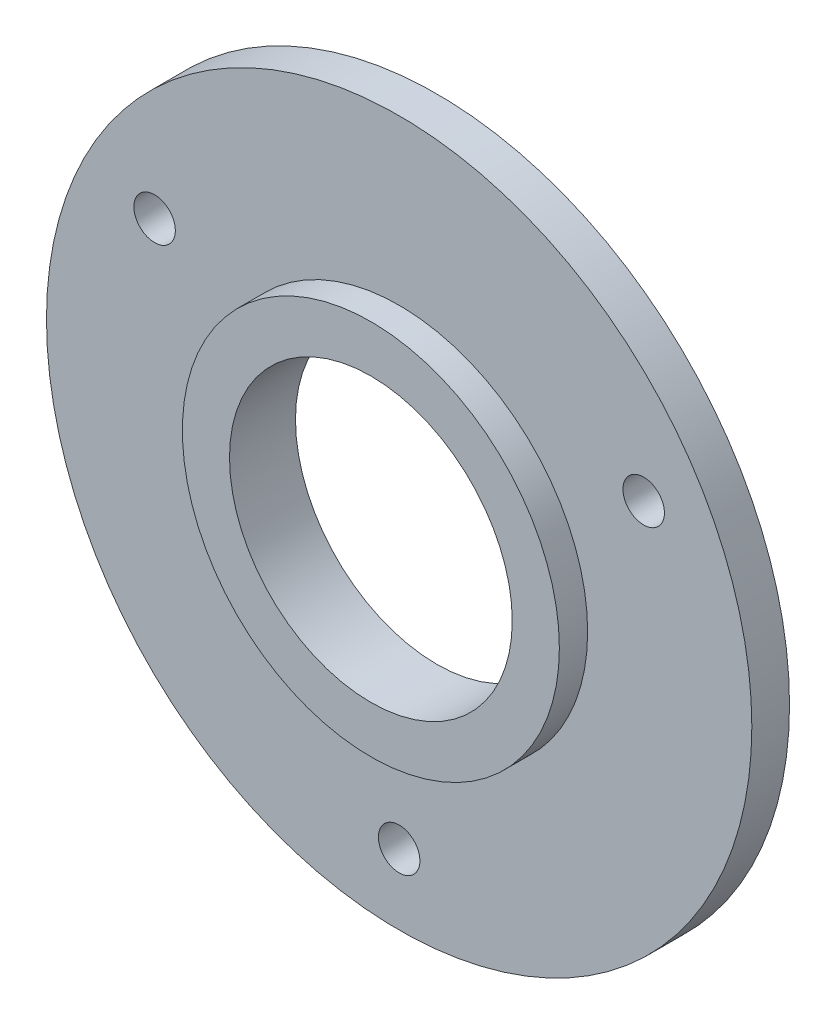
SolidWorks part; units mm, degrees
ref_plane "Front" through (0, 0, 0) normal (0, 0, 1) x (1, 0, 0)
ref_plane "Top" through (0, 0, 0) normal (0, 1, 0) x (1, 0, 0)
ref_plane "Right" through (0, 0, 0) normal (1, 0, 0) x (0, 0, -1)
sketch "Sketch1" plane through (0, 0, 0) normal (0, 0, 1) x (1, 0, 0)
  line L0 (0, 0) -> (0, -14.98) construction
  circle A0 centre (0, 0) radius 18.71
  circle A1 centre (0, -14.98) radius 1.1
  circle A2 centre (-12.9731, 7.49) radius 1.1
  circle A3 centre (12.9731, 7.49) radius 1.1
  circle A4 centre (0, 0) radius 7.5
  dimension "D1" = 37.42
  dimension "D2" = 2.2
  dimension "D5" = 15
  dimension "D4" = 14.98
  dimension "D3" = 3
extrude "Boss-Extrude1" add sketch "Sketch1" along normal blind 2
sketch "Sketch2" plane through (0, 0, 2) normal (0, 0, 1) x (1, 0, 0)
  circle A0 centre (0, 0) radius 10
  circle A1 centre (0, 0) radius 7.5 construction
  circle A2 centre (0, 0) radius 7.5
  dimension "D1" = 20
extrude "Boss-Extrude2" add sketch "Sketch2" along normal blind 1.5
